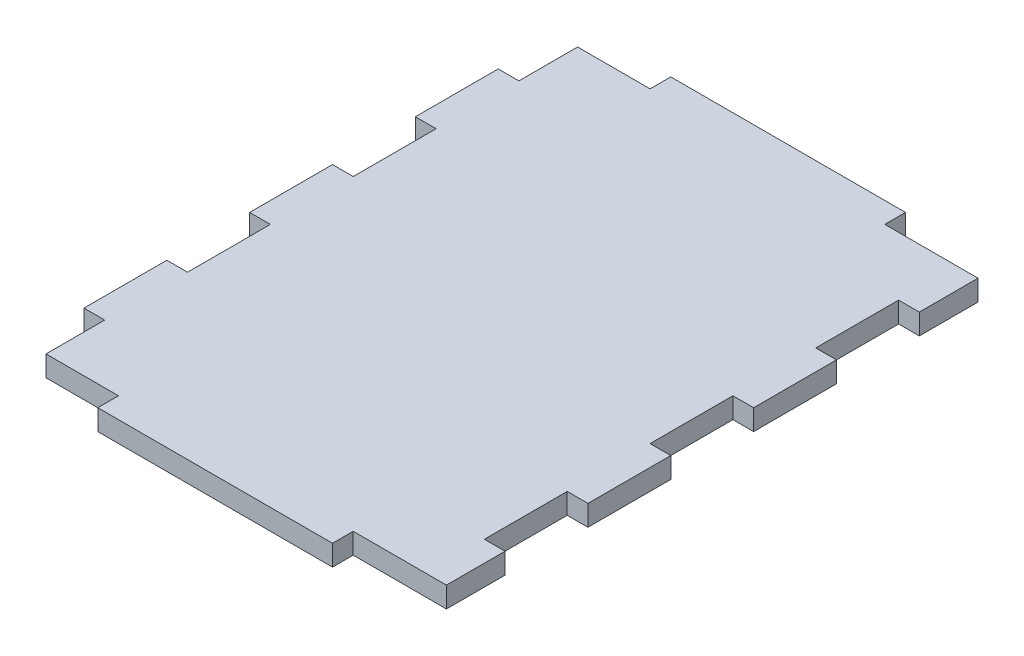
SolidWorks part; units mm, degrees
ref_plane "Alzado" through (0, 0, 0) normal (0, 0, 1) x (1, 0, 0)
ref_plane "Planta" through (0, 0, 0) normal (0, 1, 0) x (1, 0, 0)
ref_plane "Vista lateral" through (0, 0, 0) normal (1, 0, 0) x (0, 0, -1)
sketch "Croquis1" plane through (0, 0, 0) normal (0, 1, 0) x (1, 0, 0)
  line L0 (13.5, 0) -> (47.5, 0)
  line L1 (30.5, 0) -> (13.5, 0)
  line L2 (30.5, 0) -> (47.5, 0)
  line L3 (47.5, 0) -> (47.5, 3)
  line L4 (58, 35.5) -> (58, 47.5)
  line L5 (13.5, 3) -> (13.5, 0)
  line L6 (61, 3) -> (61, 11.5)
  line L7 (0, 11.5) -> (0, 23.5)
  line L8 (61, 23.5) -> (61, 35.5)
  line L9 (13.5, 80) -> (13.5, 83)
  line L10 (58, 47.5) -> (61, 47.5)
  line L11 (47.5, 83) -> (47.5, 80)
  line L12 (13.5, 83) -> (47.5, 83)
  line L13 (13.5, 80) -> (3, 80)
  line L14 (47.5, 80) -> (61, 80)
  line L15 (13.5, 3) -> (3, 3)
  line L16 (47.5, 3) -> (61, 3)
  line L17 (61, 47.5) -> (61, 59.5)
  line L18 (61, 59.5) -> (58, 59.5)
  line L19 (58, 59.5) -> (58, 71.5)
  line L20 (58, 71.5) -> (61, 71.5)
  line L21 (58, 11.5) -> (61, 11.5)
  line L22 (58, 23.5) -> (58, 11.5)
  line L23 (61, 23.5) -> (58, 23.5)
  line L24 (58, 35.5) -> (61, 35.5)
  line L26 (3, 35.5) -> (0, 35.5)
  line L27 (0, 23.5) -> (3, 23.5)
  line L29 (3, 11.5) -> (0, 11.5)
  line L30 (3, 71.5) -> (0, 71.5)
  line L31 (3, 11.5) -> (3, 3)
  line L32 (0, 59.5) -> (3, 59.5)
  line L33 (3, 47.5) -> (0, 47.5)
  line L36 (3, 80) -> (3, 71.5)
  line L37 (61, 71.5) -> (61, 80)
  line L38 (61, 47.5) -> (61, 59.5)
  line L39 (0, 59.5) -> (0, 71.5)
  line L40 (0, 35.5) -> (0, 47.5)
  line L41 (3, 59.5) -> (3, 47.5)
  line L42 (3, 35.5) -> (3, 23.5)
  dimension "D3" = 17
  dimension "D4" = 3
  dimension "D5" = 12
  dimension "D6" = 12
extrude "Saliente-Extruir1" add sketch "Croquis1" along normal blind 3 contours L26 L42 L27 L7 L29 L31 L15 L5 L0 L3 L16 L6 L21 L22 L23 L8 L24 L4 L10 L17 L18 L19 L20 L37 L14 L11 L12 L9 L13 L36 L30 L39 L32 L41 L33 L40 region at (30.5931, 0, -41.5)
